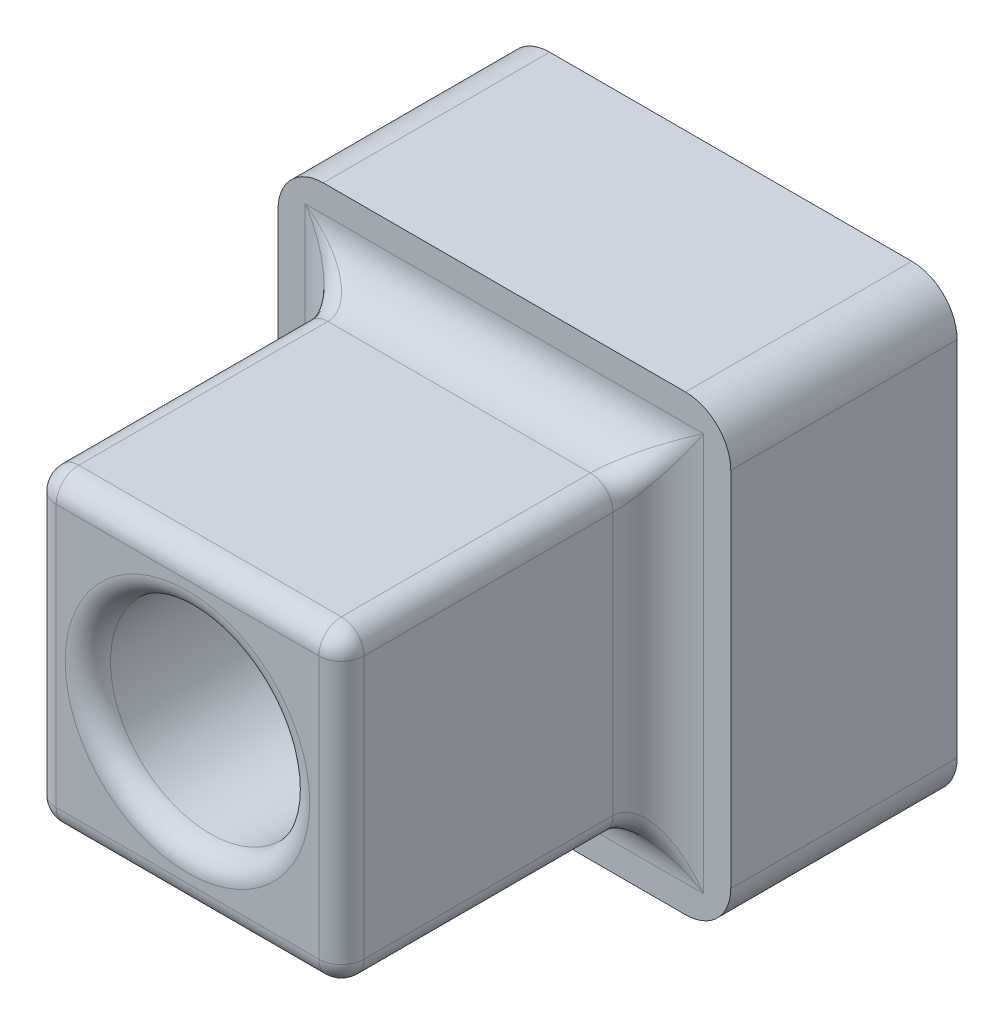
SolidWorks part; units mm, degrees
ref_plane "Front" through (0, 0, 0) normal (0, 0, 1) x (1, 0, 0)
ref_plane "Top" through (0, 0, 0) normal (0, 1, 0) x (1, 0, 0)
ref_plane "Right" through (0, 0, 0) normal (1, 0, 0) x (0, 0, -1)
sketch "Sketch1" plane through (0, 0, 0) normal (0, 0, 1) x (1, 0, 0)
  line L1 (3.4, -3.4) -> (-3.4, -3.4)
  line L2 (3.4, -3.4) -> (3.4, 3.4)
  line L3 (3.4, 3.4) -> (-3.4, 3.4)
  line L4 (-3.4, -3.4) -> (-3.4, 3.4)
  line L5 (3.4, -3.4) -> (-3.4, 3.4) construction
  line L6 (3.4, 3.4) -> (-3.4, -3.4) construction
  point P0 (0, 0)
  dimension "D1" = 6.8
  dimension "D2" = 6.8
extrude "Boss-Extrude1" add sketch "Sketch1" along normal blind 12
sketch "Sketch2" plane through (0, 0, 12) normal (0, 0, 1) x (1, 0, 0)
  circle A0 centre (0, 0) radius 2.2
  dimension "D1" = 4.4
extrude "Cut-Extrude1" cut sketch "Sketch2" against normal through all
sketch "Sketch4" plane through (0, 0, 0) normal (0, 0, -1) x (-1, 0, 0)
  line L1 (5, -5) -> (-5, -5)
  line L2 (5, -5) -> (5, 5)
  line L3 (5, 5) -> (-5, 5)
  line L4 (-5, -5) -> (-5, 5)
  line L5 (5, -5) -> (-5, 5) construction
  line L6 (5, 5) -> (-5, -5) construction
  circle A0 centre (0, 0) radius 2.2
  point P0 (0, 0)
  dimension "D3" = 4.4
  dimension "D1" = 10
  dimension "D2" = 10
extrude "Boss-Extrude3" add sketch "Sketch4" against normal blind 5
fillet "Fillet4" radius 1 4 edges at (3.4, 0, 5) (0, 3.4, 5) (0, -3.4, 5) (-3.4, 0, 5)
fillet "Fillet5" radius 1 4 edges at (-5, 5, 2.5) (-5, -5, 2.5) (5, -5, 2.5) (5, 5, 2.5)
fillet "Fillet6" radius 0.5 13 edges at (3.6929, -3.6929, 5.2929) (-3.6929, -3.6929, 5.2929) (3.6929, 3.6929, 5.2929) (-3.6929, 3.6929, 5.2929) (0, 3.4, 12) (3.4, 0, 12) (0, -3.4, 12) (-3.4, 0, 12) (2.2, 0, 12) (3.4, -3.4, 9) (-3.4, -3.4, 9) (3.4, 3.4, 9) (-3.4, 3.4, 9)
